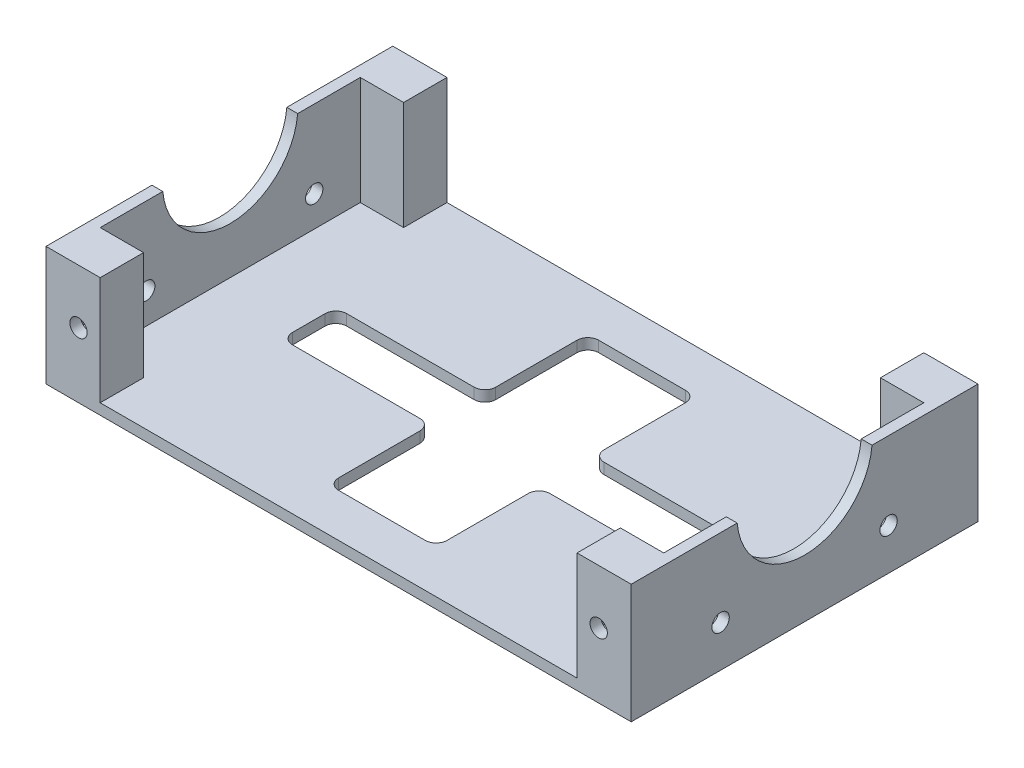
SolidWorks part; units mm, degrees
note: The reader was unsure of these and kept them because the rebuilt part matched: shared geometry of "Szkic8<2>", "Szkic8<3>", "Szkic9<2>", "Szkic9<3>".
ref_plane "Płaszczyzna przednia" through (0, 0, 0) normal (0, 0, 1) x (1, 0, 0)
ref_plane "Płaszczyzna górna" through (0, 0, 0) normal (0, 1, 0) x (1, 0, 0)
ref_plane "Płaszczyzna prawa" through (0, 0, 0) normal (1, 0, 0) x (0, 0, -1)
sketch "Szkic1" plane through (0, 0, 0) normal (0, 1, 0) x (1, 0, 0)
  line L1 (0, 0) -> (104, 0)
  line L2 (0, 0) -> (0, 64)
  line L3 (0, 64) -> (104, 64)
  line L4 (104, 0) -> (104, 64)
extrude "Dodanie-wyciągnięcie1" add sketch "Szkic1" along normal blind 2 contours L2 L1 L4 L3
sketch "Szkic2" plane through (0, 2, 0) normal (0, 1, 0) x (1, 0, 0)
  line L1 (0, 64) -> (8, 64)
  line L2 (0, 64) -> (0, 56)
  line L3 (0, 56) -> (8, 56)
  line L4 (8, 64) -> (8, 56)
  line L5 (0, 0) -> (8, 0)
  line L6 (0, 0) -> (0, 8)
  line L7 (0, 8) -> (8, 8)
  line L8 (8, 0) -> (8, 8)
  line L9 (104, 0) -> (96, 0)
  line L10 (104, 0) -> (104, 8)
  line L11 (104, 8) -> (96, 8)
  line L12 (96, 0) -> (96, 8)
  line L13 (104, 64) -> (96, 64)
  line L14 (104, 64) -> (104, 56)
  line L15 (104, 56) -> (96, 56)
  line L16 (96, 64) -> (96, 56)
extrude "Dodanie-wyciągnięcie2" add sketch "Szkic2" along normal blind 20
sketch "Szkic4" plane through (0, 0, 0) normal (-1, 0, 0) x (0, 0, 1)
  line L1 (0, 0) -> (-64, 0)
  line L2 (0, 0) -> (0, 22)
  line L3 (0, 22) -> (-64, 22)
  line L4 (-64, 0) -> (-64, 22)
  circle A0 centre (-32, 23.15) radius 12.5
  circle A1 centre (-16.5, 7.65) radius 1.6
  circle A2 centre (-47.5, 7.65) radius 1.6
  line M2 (-64, 0) -> (0, 0)
  line M3 (0, 0) -> (0, 22)
  line M4 (0, 22) -> (-8, 22)
  line M5 (-8, 22) -> (-8, 2)
  line M6 (-8, 2) -> (-56, 2)
  line M7 (-56, 2) -> (-56, 22)
  line M8 (-56, 22) -> (-64, 22)
  line M9 (-64, 22) -> (-64, 0)
extrude "Dodanie-wyciągnięcie3" add sketch "Szkic4" along normal blind 2 contours A0 L3 A2 A1 M7 M6 M5 | M9 M2 M3 M4 M5 M6 M7 M8
sketch "Szkic5" plane through (104, 0, 0) normal (1, 0, 0) x (0, 0, -1)
  line L1 (64, 0) -> (0, 0)
  line L2 (64, 0) -> (64, 22)
  line L3 (64, 22) -> (0, 22)
  line L4 (0, 0) -> (0, 22)
  circle A0 centre (32, 23.15) radius 12.5
  circle A1 centre (47.5, 7.65) radius 1.6
  circle A2 centre (16.5, 7.65) radius 1.6
  line M2 (0, 0) -> (64, 0)
  line M3 (64, 0) -> (64, 22)
  line M4 (64, 22) -> (56, 22)
  line M5 (56, 22) -> (56, 2)
  line M6 (56, 2) -> (8, 2)
  line M7 (8, 2) -> (8, 22)
  line M8 (8, 22) -> (0, 22)
  line M9 (0, 22) -> (0, 0)
extrude "Dodanie-wyciągnięcie4" add sketch "Szkic5" along normal blind 2 contours A0 L3 A2 A1 M7 M6 M5 | M9 M2 M3 M4 M5 M6 M7 M8
chamfer "Sfazowanie1" distance 2 angle 45 2 edges at (106, 0, -32) (-2, 0, -32)
sketch "Szkic6" plane through (0, 0, 0) normal (0, -1, 0) x (1, 0, 0)
  line L0 (0, 0) -> (0, -8) construction
  line L1 (0, 0) -> (0, -64) construction
  line L2 (0, -64) -> (0, -56) construction
  line L3 (104, 0) -> (104, -8) construction
  line L4 (104, -64) -> (104, 0) construction
  line L5 (104, -64) -> (104, -56) construction
  line L6 (104, -56) -> (96, -56) construction
  line L7 (0, -8) -> (8, -8) construction
  line L8 (104, -8) -> (96, -8) construction
  line L9 (0, -56) -> (8, -56) construction
  line L10 (8, -56) -> (0, -64) construction
  line L11 (8, -8) -> (0, 0) construction
  line L12 (96, -8) -> (104, 0) construction
  line L13 (96, -56) -> (104, -64) construction
  line L15 (6.8284, -6.8284) -> (6.8284, -1.1716)
  line L16 (6.8284, -1.1716) -> (1.1716, -1.1716)
  line L17 (1.1716, -1.1716) -> (1.1716, -6.8284)
  line L18 (1.1716, -6.8284) -> (6.8284, -6.8284)
  line L19 (6.8284, -57.1716) -> (1.1716, -57.1716)
  line L20 (1.1716, -57.1716) -> (1.1716, -62.8284)
  line L21 (1.1716, -62.8284) -> (6.8284, -62.8284)
  line L22 (6.8284, -62.8284) -> (6.8284, -57.1716)
  line L23 (97.1716, -57.1716) -> (97.1716, -62.8284)
  line L24 (97.1716, -62.8284) -> (102.8284, -62.8284)
  line L25 (102.8284, -62.8284) -> (102.8284, -57.1716)
  line L26 (102.8284, -57.1716) -> (97.1716, -57.1716)
  line L27 (97.1716, -6.8284) -> (102.8284, -6.8284)
  line L28 (102.8284, -6.8284) -> (102.8284, -1.1716)
  line L29 (102.8284, -1.1716) -> (97.1716, -1.1716)
  line L30 (97.1716, -1.1716) -> (97.1716, -6.8284)
  circle A0 centre (4, -4) radius 4 construction
  circle A1 centre (4, -60) radius 4 construction
  circle A2 centre (100, -60) radius 4 construction
  circle A3 centre (100, -4) radius 4 construction
  circle A4 centre (4, -4) radius 1.6
  circle A5 centre (4, -60) radius 1.6
  circle A6 centre (100, -60) radius 1.6
  circle A7 centre (100, -4) radius 1.6
extrude "Wytnij-wyciągnięcie2" cut sketch "Szkic6" against normal blind 4 contours A5 | A4 | A6 | A7 | L15 L16 L17 L18 | L27 L28 L29 L30 | L23 L24 L25 L26 | L19 L20 L21 L22
extrude "Wytnij-wyciągnięcie3" cut sketch "Szkic6" against normal blind 6.2 contours A5 | A4 | A6 | A7 | L15 L16 L17 L18 | L27 L28 L29 L30 | L23 L24 L25 L26 | L19 L20 L21 L22
extrude "Dodanie-wyciągnięcie5" add sketch "Szkic6" against normal blind 2 contours A5 | A4 | A6 | A7 | L15 L16 L17 L18 | L27 L28 L29 L30 | L23 L24 L25 L26 | L19 L20 L21 L22
sketch "Szkic8" plane through (0, 0, -64) normal (0, 0, -1) x (-1, 0, 0)
  line L0 (0, 0) -> (0, 8) construction
  line L1 (-8, 2) -> (-8, 8) construction
  line L2 (-8, 22) -> (-8, 2) construction
  line L3 (-8, 8) -> (-8, 16) construction
  line L4 (0, 8) -> (0, 16) construction
  line L5 (0, 16) -> (-8, 8) construction
  line L6 (-104, 0) -> (-104, 8) construction
  line L7 (-104, 8) -> (-104, 16) construction
  line L8 (-104, 16) -> (-96, 16) construction
  line L9 (-96, 22) -> (-96, 2) construction
  line L10 (-96, 16) -> (-104, 8) construction
  line L12 (-6.8284, 9.1716) -> (-1.1716, 9.1716)
  line L13 (-1.1716, 9.1716) -> (-1.1716, 14.8284)
  line L14 (-1.1716, 14.8284) -> (-6.8284, 14.8284)
  line L15 (-6.8284, 14.8284) -> (-6.8284, 9.1716)
  line L16 (-102.8284, 9.1716) -> (-97.1716, 9.1716)
  line L17 (-97.1716, 9.1716) -> (-97.1716, 14.8284)
  line L18 (-97.1716, 14.8284) -> (-102.8284, 14.8284)
  line L19 (-102.8284, 14.8284) -> (-102.8284, 9.1716)
  circle A0 centre (-4, 12) radius 1.6
  circle A1 centre (-100, 12) radius 1.6
  circle A2 centre (-4, 12) radius 4 construction
  circle A3 centre (-100, 12) radius 4 construction
extrude "Wytnij-wyciągnięcie4" cut sketch "Szkic8" against normal blind 4
extrude "Wytnij-wyciągnięcie5" cut sketch "Szkic8<2>" against normal blind 4.2 contours A1 | A0
sketch "Szkic8<2>" plane through (0, 0, -64) normal (0, 0, -1) x (-1, 0, 0) same geometry as "Szkic8"
extrude "Dodanie-wyciągnięcie6" add sketch "Szkic8<3>" against normal blind 2 contours L18 L19 L16 L17 | A1 | L14 L15 L12 L13 | A0
sketch "Szkic8<3>" plane through (0, 0, -64) normal (0, 0, -1) x (-1, 0, 0) same geometry as "Szkic8"
sketch "Szkic9" plane through (0, 0, 0) normal (0, 0, 1) x (1, 0, 0)
  line L0 (104, 0) -> (104, 8) construction
  line L1 (104, 8) -> (104, 16) construction
  line L2 (104, 16) -> (96, 16) construction
  line L3 (96, 22) -> (96, 2) construction
  line L4 (96, 16) -> (104, 8) construction
  line L5 (0, 0) -> (0, 8) construction
  line L6 (0, 8) -> (0, 16) construction
  line L7 (0, 16) -> (8, 16) construction
  line L8 (8, 22) -> (8, 2) construction
  line L9 (8, 16) -> (0, 8) construction
  line L11 (97.1716, 14.8284) -> (97.1716, 9.1716)
  line L12 (97.1716, 9.1716) -> (102.8284, 9.1716)
  line L13 (102.8284, 9.1716) -> (102.8284, 14.8284)
  line L14 (102.8284, 14.8284) -> (97.1716, 14.8284)
  line L15 (1.1716, 9.1716) -> (6.8284, 9.1716)
  line L16 (6.8284, 9.1716) -> (6.8284, 14.8284)
  line L17 (6.8284, 14.8284) -> (1.1716, 14.8284)
  line L18 (1.1716, 14.8284) -> (1.1716, 9.1716)
  circle A0 centre (100, 12) radius 1.6
  circle A1 centre (4, 12) radius 1.6
  circle A2 centre (100, 12) radius 4 construction
  circle A3 centre (4, 12) radius 4 construction
extrude "Wytnij-wyciągnięcie6" cut sketch "Szkic9" against normal blind 4
extrude "Wytnij-wyciągnięcie7" cut sketch "Szkic9<2>" against normal blind 4.2 contours A1 | A0
sketch "Szkic9<2>" plane through (0, 0, 0) normal (0, 0, 1) x (1, 0, 0) same geometry as "Szkic9"
extrude "Dodanie-wyciągnięcie7" add sketch "Szkic9<3>" against normal blind 2 contours A1 | L17 L18 L15 L16 | A0 | L14 L11 L12 L13
sketch "Szkic9<3>" plane through (0, 0, 0) normal (0, 0, 1) x (1, 0, 0) same geometry as "Szkic9"
sketch "Szkic10" plane through (0, 0, 0) normal (0, -1, 0) x (1, 0, 0)
  line L0 (104, -56) -> (96, -56) construction
  line L1 (104, -64) -> (104, 0) construction
  line L2 (96, -56) -> (96, -64) construction
  line L3 (0, -64) -> (104, -64) construction
  line L4 (8, -64) -> (8, -56) construction
  line L5 (8, -56) -> (0, -56) construction
  line L6 (0, 0) -> (0, -64) construction
  line L7 (0, -8) -> (8, -8) construction
  line L8 (8, -8) -> (8, 0) construction
  line L9 (0, 0) -> (104, 0) construction
  line L10 (104, -8) -> (96, -8) construction
  line L11 (96, -8) -> (96, 0) construction
  line L12 (96, -8) -> (8, -8) construction
  line L13 (8, -8) -> (8, -56) construction
  line L14 (8, -56) -> (96, -56) construction
  line L15 (96, -56) -> (96, -8) construction
  line L16 (96, -32) -> (8, -32) construction
  line L17 (52, -56) -> (52, -32) construction
  line L18 (52, -32) -> (52, -8) construction
  line L26 (42, -56) -> (62, -56)
  line L27 (42, -56) -> (42, -8)
  line L28 (14.5, -37) -> (89.5, -37)
  line L29 (14.5, -37) -> (14.5, -27)
  line L30 (14.5, -27) -> (89.5, -27)
  line L31 (89.5, -37) -> (89.5, -27)
  line L32 (14.5, -37) -> (89.5, -27) construction
  line L33 (14.5, -27) -> (89.5, -37) construction
  line L34 (42, -8) -> (62, -8)
  line L35 (62, -56) -> (62, -8)
  line L36 (42, -56) -> (62, -8) construction
  line L37 (42, -8) -> (62, -56) construction
extrude "Wytnij-wyciągnięcie8" cut sketch "Szkic10" against normal blind 9 contours L28 L35 L30 L27 | L30 L29 L28 L27 | L30 L35 L34 L27 | L26 L35 L28 L27 | L35 L28 L31 L30
sketch "Szkic11" plane through (0, 0, 0) normal (0, 0, 1) x (1, 0, 0)
  line L0 (-2, 2) -> (0, 0) construction
  line L1 (-2, 2) -> (0, 2)
  line L2 (-2, 2) -> (-2, 0)
  line L3 (-2, 0) -> (0, 0)
  line L4 (0, 2) -> (0, 0)
  line L5 (0, 0) -> (104, 0) construction
  line L6 (104, 0) -> (106, 2) construction
  line L7 (104, 0) -> (106, 0)
  line L8 (104, 0) -> (104, 2)
  line L9 (104, 2) -> (106, 2)
  line L10 (106, 0) -> (106, 2)
extrude "Dodanie-wyciągnięcie8" add sketch "Szkic11" against normal up to vertex (64 mm away)
fillet "Zaokrąglenie1" radius 2 12 edges at (14.5, 1, -27) (14.5, 1, -37) (42, 1, -37) (42, 1, -56) (62, 1, -56) (62, 1, -37) (89.5, 1, -37) (89.5, 1, -27) (62, 1, -27) (62, 1, -8) (42, 1, -8) (42, 1, -27)
